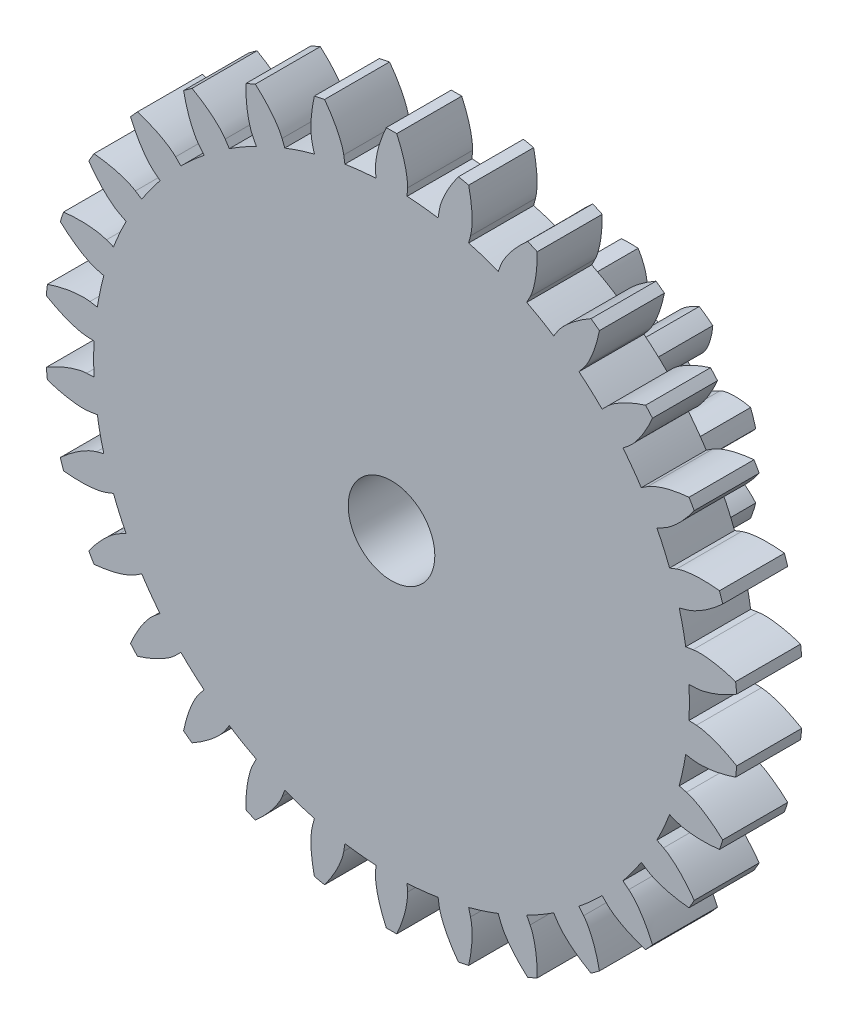
SolidWorks part; units mm, degrees
ref_plane "前视基准面" through (0, 0, 0) normal (0, 0, 1) x (1, 0, 0)
ref_plane "上视基准面" through (0, 0, 0) normal (0, 1, 0) x (1, 0, 0)
ref_plane "右视基准面" through (0, 0, 0) normal (1, 0, 0) x (0, 0, -1)
other "Configuration Table"
sketch "草图1" plane through (0, 0, 0) normal (0, 0, 1) x (1, 0, 0)
  line L0 (0, 0) -> (2.5, 0) construction
  line L1 (0, 0) -> (2.4692, 0.3911) construction
  line L2 (0, 0) -> (2.324, 0.3431)
  line L3 (2.4692, 0.3911) -> (2.4692, -0.3911) construction
  line L4 (0, 0) -> (2.324, -0.3431)
  circle A0 centre (0, 0) radius 3
  circle A1 centre (0, 0) radius 2.5 construction
  circle A2 centre (0, 0) radius 1.875
  circle A3 centre (0, 0) radius 2.3492 construction
  circle A4 centre (0, 0) radius 1
  spline S0 degree 4 poles (2.324, 0.3431) (2.3418, 0.3457) (2.3907, 0.3567) (2.48, 0.3921) (2.6156, 0.4687) (2.774, 0.5944) (2.9524, 0.7829) (3.1261, 1.0328) (3.2755, 1.3318) (3.3905, 1.6731) (3.4623, 2.0258) (3.4939, 2.3843) (3.4875, 2.7617) (3.431, 3.2258) (3.293, 3.7669) (3.0427, 4.3657) (2.6648, 4.9798) (2.2034, 5.533) (1.6708, 6.0186) (1.0824, 6.4323) (0.4456, 6.7712) (-0.2216, 7.0345) (-0.9214, 7.2211) (-1.5352, 7.3195) (-2.0864, 7.356) (-2.4818, 7.3587) (-2.8333, 7.3427) (-3.0656, 7.3237) (-3.3922, 7.2873) (-3.6372, 7.2455) (-3.8821, 7.2011) (-4.0043, 7.1711) (-4.0832, 7.1539) knots 0 0 0 0 0 0.005604 0.015718 0.02996 0.048734 0.068727 0.096889 0.125051 0.153212 0.181374 0.209535 0.237696 0.271429 0.327752 0.384075 0.440398 0.496721 0.553044 0.609367 0.66569 0.722013 0.778336 0.834659 0.86282 0.890982 0.909091 0.931818 0.954545 0.977273 1 1 1 1 1 construction
  spline S1 degree 4 poles (2.324, 0.3431) (2.3418, 0.3457) (2.3907, 0.3567) (2.48, 0.3921) (2.6156, 0.4687) (2.774, 0.5944) (2.9524, 0.7829) (3.1261, 1.0328) (3.2755, 1.3318) (3.3905, 1.6731) (3.4623, 2.0258) (3.4939, 2.3843) (3.4875, 2.7617) (3.431, 3.2258) (3.293, 3.7669) (3.0427, 4.3657) (2.6648, 4.9798) (2.2034, 5.533) (1.6708, 6.0186) (1.0824, 6.4323) (0.4456, 6.7712) (-0.2216, 7.0345) (-0.9214, 7.2211) (-1.5352, 7.3195) (-2.0864, 7.356) (-2.4818, 7.3587) (-2.7511, 7.3465) (-2.8848, 7.3375) (-2.9371, 7.3334) knots 0 0 0 0 0 0.005604 0.015718 0.02996 0.048734 0.068727 0.096889 0.125051 0.153212 0.181374 0.209535 0.237696 0.271429 0.327752 0.384075 0.440398 0.496721 0.553044 0.609367 0.66569 0.722013 0.778336 0.834659 0.86282 0.890982 0.909091 0.909091 0.909091 0.909091 0.909091
  spline S2 degree 4 poles (2.324, -0.3431) (2.3418, -0.3457) (2.3907, -0.3567) (2.48, -0.3921) (2.6156, -0.4687) (2.774, -0.5944) (2.9524, -0.7829) (3.1261, -1.0328) (3.2755, -1.3318) (3.3905, -1.6731) (3.4623, -2.0258) (3.4939, -2.3843) (3.4875, -2.7617) (3.431, -3.2258) (3.293, -3.7669) (3.0427, -4.3657) (2.6648, -4.9798) (2.2034, -5.533) (1.6708, -6.0186) (1.0824, -6.4323) (0.4456, -6.7712) (-0.2216, -7.0345) (-0.9214, -7.2211) (-1.5352, -7.3195) (-2.0864, -7.356) (-2.4818, -7.3587) (-2.8333, -7.3427) (-3.0656, -7.3237) (-3.3922, -7.2873) (-3.6372, -7.2455) (-3.8821, -7.2011) (-4.0043, -7.1711) (-4.0832, -7.1539) knots 0 0 0 0 0 0.005604 0.015718 0.02996 0.048734 0.068727 0.096889 0.125051 0.153212 0.181374 0.209535 0.237696 0.271429 0.327752 0.384075 0.440398 0.496721 0.553044 0.609367 0.66569 0.722013 0.778336 0.834659 0.86282 0.890982 0.909091 0.931818 0.954545 0.977273 1 1 1 1 1 construction
  spline S3 degree 4 poles (2.324, -0.3431) (2.3418, -0.3457) (2.3907, -0.3567) (2.48, -0.3921) (2.6156, -0.4687) (2.774, -0.5944) (2.9524, -0.7829) (3.1261, -1.0328) (3.2755, -1.3318) (3.3905, -1.6731) (3.4623, -2.0258) (3.4939, -2.3843) (3.4875, -2.7617) (3.431, -3.2258) (3.293, -3.7669) (3.0427, -4.3657) (2.6648, -4.9798) (2.2034, -5.533) (1.6708, -6.0186) (1.0824, -6.4323) (0.4456, -6.7712) (-0.2216, -7.0345) (-0.9214, -7.2211) (-1.5352, -7.3195) (-2.0864, -7.356) (-2.4818, -7.3587) (-2.7511, -7.3465) (-2.8848, -7.3375) (-2.9371, -7.3334) knots 0 0 0 0 0 0.005604 0.015718 0.02996 0.048734 0.068727 0.096889 0.125051 0.153212 0.181374 0.209535 0.237696 0.271429 0.327752 0.384075 0.440398 0.496721 0.553044 0.609367 0.66569 0.722013 0.778336 0.834659 0.86282 0.890982 0.909091 0.909091 0.909091 0.909091 0.909091
  point P15 (2.4692, 0)
  dimension "齿顶圆直径" = 6
  dimension "分度圆直径" = 5
  dimension "齿根圆直径" = 3.75
  dimension "基圆直径" = 4.6985
  dimension "内孔直径" = 2
  dimension "渐近线镜像线夹角" = 9
extrude "凸台-拉伸1" add sketch "草图1" along normal blind 4 contours A0 | A4
extrude "切除-拉伸1" cut sketch "草图1<3>" along normal through all contours A2 S3 A0 S1 region at (2.52, 0, 0)
sketch "草图1<3>" plane through (0, 0, 0) normal (0, 0, 1) x (1, 0, 0) same geometry as "草图1"
pattern_circular "阵列(圆周)1" count 10 every 36 about axis through (0, 0, 4) along (0, 0, 1) of "切除-拉伸1"
sketch "草图2" plane through (0, 0, 4) normal (0, 0, 1) x (1, 0, 0)
  line L0 (0, 0) -> (7.5, 0) construction
  line L1 (0, 0) -> (7.038, 0.3688)
  line L2 (0, 0) -> (7.038, -0.3688)
  line L3 (7.038, 0.3688) -> (7.038, -0.3688) construction
  circle A0 centre (0, 0) radius 7.5 construction
  circle A1 centre (0, 0) radius 7.0477 construction
  circle A2 centre (0, 0) radius 6.875
  circle A3 centre (0, 0) radius 8
  circle A4 centre (0, 0) radius 1
  spline S0 degree 4 poles (7.038, -0.3688) (7.0648, -0.3703) (7.1181, -0.3756) (7.2661, -0.4036) (7.54, -0.4903) (7.9387, -0.6789) (8.4412, -1.0177) (9.0178, -1.5414) (9.5944, -2.2492) (10.1095, -3.1096) (10.5312, -4.1044) (10.8266, -5.1431) (11.0027, -6.2081) (11.0697, -7.3387) (11.0063, -8.7398) (10.7169, -10.3898) (10.1042, -12.238) (9.1146, -14.161) (7.8594, -15.921) (6.3787, -17.4949) (4.7097, -18.8667) (3.115, -19.8807) (1.6719, -20.6128) (0.4283, -21.1308) (-0.5886, -21.4897) (-1.622, -21.7931) (-2.6724, -22.0413) (-3.73, -22.2344) (-4.6701, -22.3557) (-5.4675, -22.426) (-6.1046, -22.4596) (-6.5222, -22.4739) (-6.9919, -22.4794) (-7.2978, -22.4782) (-7.7905, -22.469) (-8.174, -22.4512) (-8.6389, -22.4248) (-9.053, -22.3901) (-9.4984, -22.3472) (-9.9204, -22.296) (-10.2509, -22.2515) (-10.4614, -22.2192) (-10.5706, -22.2024) knots 0 0 0 0 0 0.002802 0.005604 0.015718 0.02996 0.048734 0.068727 0.096889 0.125051 0.153212 0.181374 0.209535 0.237696 0.271429 0.327752 0.384075 0.440398 0.496721 0.553044 0.609367 0.66569 0.693852 0.722013 0.750174 0.778336 0.806497 0.834659 0.86282 0.876901 0.890982 0.900036 0.909091 0.920455 0.931818 0.943182 0.954545 0.965909 0.977273 0.988636 1 1 1 1 1 construction
  spline S1 degree 4 poles (7.038, -0.3688) (7.0648, -0.3703) (7.1181, -0.3756) (7.2661, -0.4036) (7.54, -0.4903) (7.9387, -0.6789) (8.4412, -1.0177) (9.0178, -1.5414) (9.5944, -2.2492) (10.1095, -3.1096) (10.5312, -4.1044) (10.8266, -5.1431) (11.0027, -6.2081) (11.0697, -7.3387) (11.0063, -8.7398) (10.7169, -10.3898) (10.1042, -12.238) (9.1146, -14.161) (7.8594, -15.921) (6.3787, -17.4949) (4.7097, -18.8667) (3.115, -19.8807) (1.6719, -20.6128) (0.4283, -21.1308) (-0.5886, -21.4897) (-1.622, -21.7931) (-2.6724, -22.0413) (-3.73, -22.2344) (-4.6701, -22.3557) (-5.4675, -22.426) (-6.1046, -22.4596) (-6.5222, -22.4739) (-6.8693, -22.478) (-7.028, -22.4785) (-7.1067, -22.4783) knots 0 0 0 0 0 0.002802 0.005604 0.015718 0.02996 0.048734 0.068727 0.096889 0.125051 0.153212 0.181374 0.209535 0.237696 0.271429 0.327752 0.384075 0.440398 0.496721 0.553044 0.609367 0.66569 0.693852 0.722013 0.750174 0.778336 0.806497 0.834659 0.86282 0.876901 0.890982 0.900036 0.909091 0.909091 0.909091 0.909091 0.909091
  spline S2 degree 4 poles (7.038, 0.3688) (7.0648, 0.3703) (7.1181, 0.3756) (7.2661, 0.4036) (7.54, 0.4903) (7.9387, 0.6789) (8.4412, 1.0177) (9.0178, 1.5414) (9.5944, 2.2492) (10.1095, 3.1096) (10.5312, 4.1044) (10.8266, 5.1431) (11.0027, 6.2081) (11.0697, 7.3387) (11.0063, 8.7398) (10.7169, 10.3898) (10.1042, 12.238) (9.1146, 14.161) (7.8594, 15.921) (6.3787, 17.4949) (4.7097, 18.8667) (3.115, 19.8807) (1.6719, 20.6128) (0.4283, 21.1308) (-0.5886, 21.4897) (-1.622, 21.7931) (-2.6724, 22.0413) (-3.73, 22.2344) (-4.6701, 22.3557) (-5.4675, 22.426) (-6.1046, 22.4596) (-6.5222, 22.4739) (-6.9919, 22.4794) (-7.2978, 22.4782) (-7.7905, 22.469) (-8.174, 22.4512) (-8.6389, 22.4248) (-9.053, 22.3901) (-9.4984, 22.3472) (-9.9204, 22.296) (-10.2509, 22.2515) (-10.4614, 22.2192) (-10.5706, 22.2024) knots 0 0 0 0 0 0.002802 0.005604 0.015718 0.02996 0.048734 0.068727 0.096889 0.125051 0.153212 0.181374 0.209535 0.237696 0.271429 0.327752 0.384075 0.440398 0.496721 0.553044 0.609367 0.66569 0.693852 0.722013 0.750174 0.778336 0.806497 0.834659 0.86282 0.876901 0.890982 0.900036 0.909091 0.920455 0.931818 0.943182 0.954545 0.965909 0.977273 0.988636 1 1 1 1 1 construction
  spline S3 degree 4 poles (7.038, 0.3688) (7.0648, 0.3703) (7.1181, 0.3756) (7.2661, 0.4036) (7.54, 0.4903) (7.9387, 0.6789) (8.4412, 1.0177) (9.0178, 1.5414) (9.5944, 2.2492) (10.1095, 3.1096) (10.5312, 4.1044) (10.8266, 5.1431) (11.0027, 6.2081) (11.0697, 7.3387) (11.0063, 8.7398) (10.7169, 10.3898) (10.1042, 12.238) (9.1146, 14.161) (7.8594, 15.921) (6.3787, 17.4949) (4.7097, 18.8667) (3.115, 19.8807) (1.6719, 20.6128) (0.4283, 21.1308) (-0.5886, 21.4897) (-1.622, 21.7931) (-2.6724, 22.0413) (-3.73, 22.2344) (-4.6701, 22.3557) (-5.4675, 22.426) (-6.1046, 22.4596) (-6.5222, 22.4739) (-6.8693, 22.478) (-7.028, 22.4785) (-7.1067, 22.4783) knots 0 0 0 0 0 0.002802 0.005604 0.015718 0.02996 0.048734 0.068727 0.096889 0.125051 0.153212 0.181374 0.209535 0.237696 0.271429 0.327752 0.384075 0.440398 0.496721 0.553044 0.609367 0.66569 0.693852 0.722013 0.750174 0.778336 0.806497 0.834659 0.86282 0.876901 0.890982 0.900036 0.909091 0.909091 0.909091 0.909091 0.909091
  point P16 (7.038, 0)
  dimension "内孔直径" = 2
  dimension "分度圆直径" = 15
  dimension "齿顶圆直径" = 16
  dimension "基圆直径" = 14.0954
  dimension "齿根圆直径" = 13.75
  dimension "渐开线镜像线夹角" = 3
extrude "凸台-拉伸2" add sketch "草图2" along normal blind 1.5 contours A3 | A4
extrude "切除-拉伸3" cut sketch "草图2<3>" along normal through all contours S3 L1 A2 L2 S1 A3 region at (7.5024, 0, 4)
sketch "草图2<3>" plane through (0, 0, 4) normal (0, 0, 1) x (1, 0, 0) same geometry as "草图2"
pattern_circular "阵列(圆周)2" count 30 over 360 about axis through (0, 0, 5.5) along (0, 0, 1) of "切除-拉伸3"
equation "\"m\"= 0.5'模数"
equation "\"z\"= 10'齿数"
equation "\"a\"= 20度'压力角"
equation "\"d\"= \"m\" * \"z\"'分度圆直径"
equation "\"da\"= ( \"z\" + 2 ) * \"m\"'齿顶圆直径"
equation "\"df\"= ( \"z\" - 2.5 ) * \"m\"'齿根圆直径"
equation "\"s\"= 0.5 * PI * \"m\"'分度圆齿厚"
equation "\"r\"= 0.38 * \"m\"'齿根圆角"
equation "\"B\"= 0.3 * \"d\"'齿厚"
equation "\"db\"= \"m\" * \"z\" * cos ( \"a\" )'基圆直径"
equation "\"rb\"= \"db\" / 2'基圆半径"
equation "\"齿顶圆直径@草图1\"= \"da\""
equation "\"分度圆直径@草图1\"= \"d\""
equation "\"齿根圆直径@草图1\"= \"df\""
equation "\"基圆直径@草图1\"= \"db\""
equation "\"渐近线镜像线夹角@草图1\"= 360 / 4 / \"z\""
equation "\"h\"= 4'齿轮厚度"
equation "\"ir\"= 2'内孔直径"
equation "\"内孔直径@草图1\"= \"ir\""
equation "\"齿轮厚@凸台-拉伸1\"= \"h\""
equation "\"齿轮夹角@阵列(圆周)1\"= 360 / \"z\""
equation "\"齿数@阵列(圆周)1\"= \"z\""
equation "\"m1\"= 0.5'模数"
equation "\"z1\"= 30'齿数"
equation "\"a1\"= 20度'压力角"
equation "\"d1\"= \"m1\" * \"z1\"'分度圆直径"
equation "\"da1\"= ( \"z1\" + 2 ) * \"m1\"'齿顶圆直径"
equation "\"df1\"= ( \"z1\" - 2.5 ) * \"m1\"'齿根圆直径"
equation "\"s1\"= 0.5 * PI * \"m1\"'分度圆齿厚"
equation "\"r1\"= 0.38 * \"m1\"'齿根圆角"
equation "\"B1\"= 0.3 * \"d1\"'齿厚"
equation "\"db1\"= \"m1\" * \"z1\" * cos ( \"a1\" )'基圆直径"
equation "\"rb1\"= \"db1\" / 2'基圆半径"
equation "\"分度圆直径@草图2\"= \"d1\""
equation "\"齿顶圆直径@草图2\"= \"da1\""
equation "\"基圆直径@草图2\"= \"db1\""
equation "\"齿根圆直径@草图2\"= \"df1\""
equation "\"渐开线镜像线夹角@草图2\"= 360 / 4 / \"z1\""
equation "\"内孔直径@草图2\"= \"ir\""
equation "\"二层齿轮厚@凸台-拉伸2\" = \"h1\""
equation "\"h1\"= 1.5'齿轮厚度"
equation "\"二层齿数@阵列(圆周)2\"= \"z1\""
